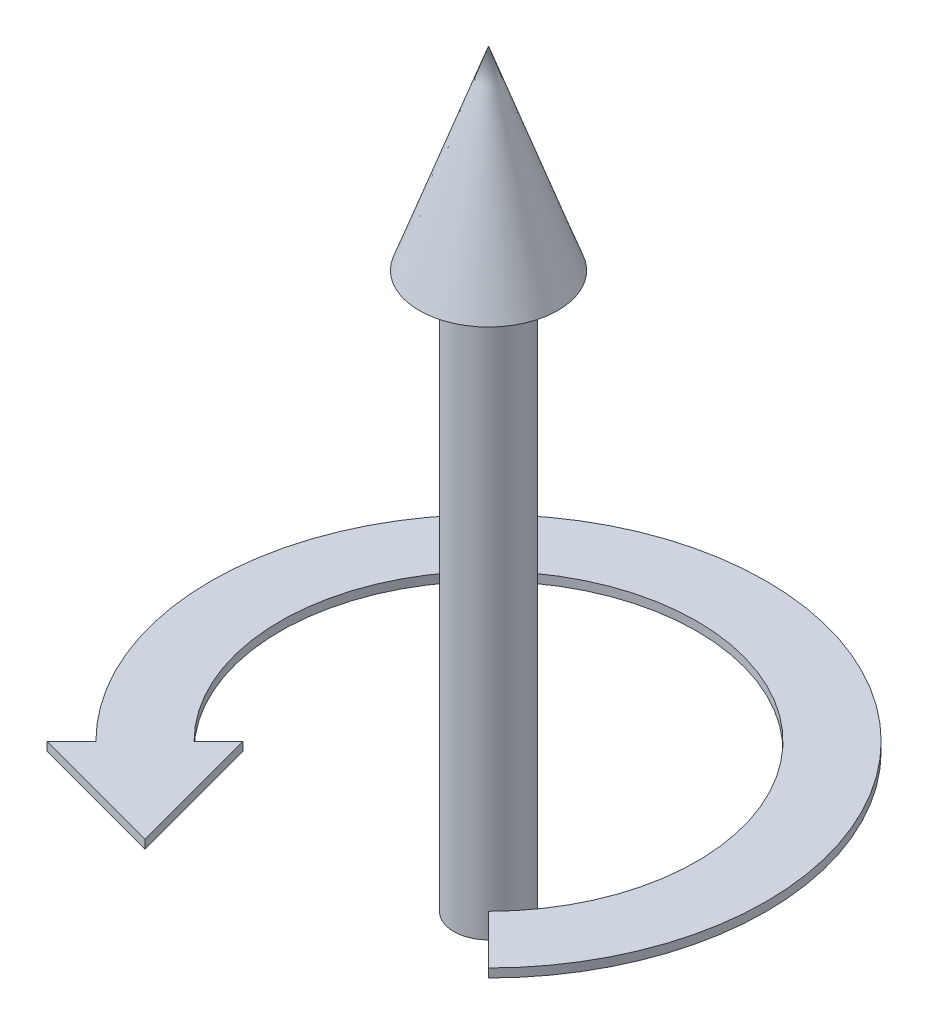
SolidWorks part; units mm, degrees
ref_plane "Front Plane" through (0, 0, 0) normal (0, 0, 1) x (1, 0, 0)
ref_plane "Top Plane" through (0, 0, 0) normal (0, 1, 0) x (1, 0, 0)
ref_plane "Right Plane" through (0, 0, 0) normal (1, 0, 0) x (0, 0, -1)
sketch "Sketch1" plane through (0, 0, 0) normal (0, 1, 0) x (1, 0, 0)
  circle A0 centre (0, 0) radius 1.5875
  dimension "D1" = 3.175
extrude "Boss-Extrude1" add sketch "Sketch1" along normal blind 25.4
sketch "Sketch3" plane through (0, 0, 0) normal (0, 0, 1) x (1, 0, 0)
  line L0 (1.5875, 25.4) -> (-1.5875, 25.4) construction
  line L1 (1.5875, 25.4) -> (-1.5875, 25.4) construction
  line L2 (0, 25.4) -> (0, 34.29)
  line L3 (0, 34.29) -> (3.175, 25.4)
  line L4 (3.175, 25.4) -> (1.5875, 25.4)
  line L5 (0, 25.4) -> (1.5875, 25.4)
  dimension "D1" = 8.89
  dimension "D2" = 3.175
revolve "Revolve1" add sketch "Sketch3" angle 360 about L2
sketch "Sketch4" plane through (0, 0, 0) normal (0, -1, 0) x (1, 0, 0)
  line L0 (0, -12.7) -> (0, 0) construction
  line L1 (-8.9803, 8.9803) -> (0, 0) construction
  line L2 (0, 0) -> (8.9803, 8.9803) construction
  line L3 (-6.7352, 6.7352) -> (-5.6127, 5.6127)
  line L4 (-5.6127, 5.6127) -> (-3.9692, 11.7463)
  line L5 (-3.9692, 11.7463) -> (-10.1028, 10.1028)
  line L6 (-10.1028, 10.1028) -> (-8.9803, 8.9803)
  line L7 (6.7352, 6.7352) -> (8.9803, 8.9803)
  arc A0 (-8.9803, 8.9803) -> (8.9803, 8.9803) centre (0, 0) ccw
  arc A1 (-6.7352, 6.7352) -> (6.7352, 6.7352) centre (0, 0) ccw
  dimension "D1" = 3.175
  dimension "D2" = 19.05
  dimension "D3" = 45
  dimension "D4" = 45
  dimension "D5" = 60
  dimension "D6" = 1.5875
extrude "Boss-Extrude2" add sketch "Sketch4" against normal blind 0.3969 from offset 6.35 separate body offset against normal yes
